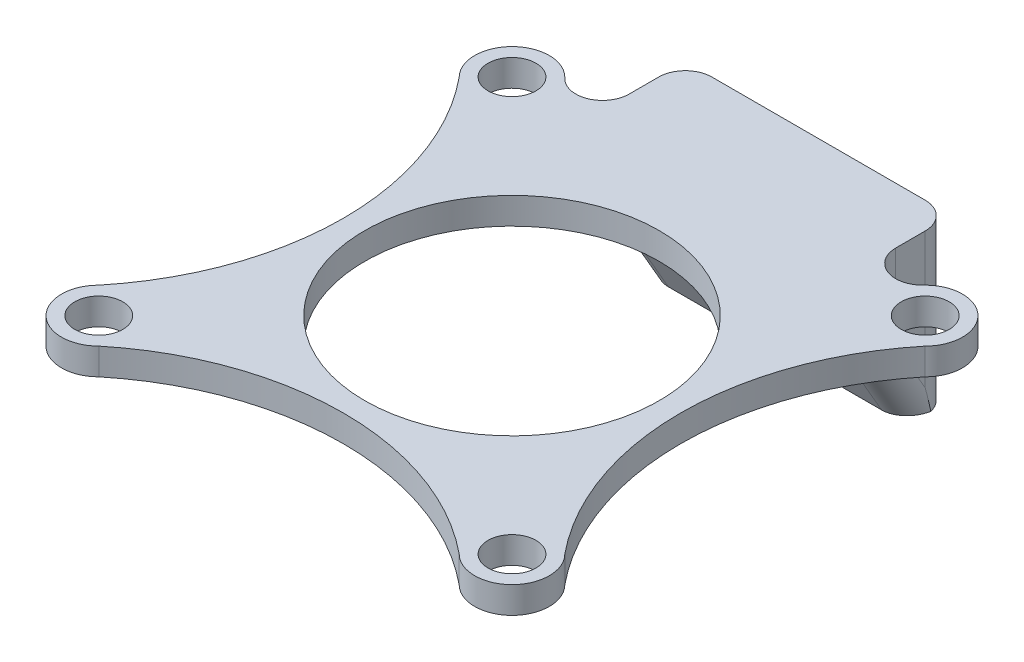
SolidWorks part; units mm, degrees
ref_plane "前视基准面" through (0, 0, 0) normal (0, 0, 1) x (1, 0, 0)
ref_plane "上视基准面" through (0, 0, 0) normal (0, 1, 0) x (1, 0, 0)
ref_plane "右视基准面" through (0, 0, 0) normal (1, 0, 0) x (0, 0, -1)
sketch "草图1" plane through (0, 0, 0) normal (0, 1, 0) x (1, 0, 0)
  line L0 (0, 80.3703) -> (0, -68.6055) construction
  line L1 (-122.6133, 0) -> (117.4549, 0) construction
  line L2 (-122.6133, -15.5) -> (117.4549, -15.5) construction
  line L3 (-15.5, 80.3703) -> (-15.5, -68.6055) construction
  line L4 (-122.6133, 15.5) -> (117.4549, 15.5) construction
  line L5 (15.5, 80.3703) -> (15.5, -68.6055) construction
  line L6 (15.5, 15.5) -> (-15.5, -15.5) construction
  line L7 (13.5201, 17.4799) -> (-17.4799, -13.5201)
  line L8 (17.4799, 13.5201) -> (-13.5201, -17.4799)
  line L9 (15.5, -15.5) -> (-15.5, 15.5) construction
  line L10 (17.4799, -13.5201) -> (-13.5201, 17.4799)
  line L11 (13.5201, -17.4799) -> (-17.4799, 13.5201)
  line L12 (-8, 23) -> (8, 23)
  line L13 (-122.6133, 16) -> (117.4549, 16) construction
  line L14 (-10, 21) -> (-10, 13.9598)
  line L15 (10, 21) -> (10, 13.9598)
  line L16 (-122.6133, 23) -> (117.4549, 23) construction
  line L17 (10, 80.3703) -> (10, -68.6055) construction
  line L19 (-10, 80.3703) -> (-10, -68.6055) construction
  circle A0 centre (0, 0) radius 11.05
  circle A3 centre (-15.5, 15.5) radius 1.8
  circle A4 centre (15.5, 15.5) radius 1.8
  circle A5 centre (15.5, -15.5) radius 1.8
  circle A6 centre (-15.5, -15.5) radius 1.8
  arc A24 (13.5201, 17.4799) -> (17.4799, 13.5201) centre (15.5, 15.5) cw
  arc A25 (-17.4799, -13.5201) -> (-13.5201, -17.4799) centre (-15.5, -15.5) ccw
  arc A26 (17.4799, -13.5201) -> (13.5201, -17.4799) centre (15.5, -15.5) cw
  arc A27 (-13.5201, 17.4799) -> (-17.4799, 13.5201) centre (-15.5, 15.5) ccw
  circle A28 centre (0, 0) radius 12.65
  arc A32 (-10, 21) -> (-8, 23) centre (-8, 21) cw
  arc A33 (8, 23) -> (10, 21) centre (8, 21) cw
  arc A34 (17.4799, 13.5201) -> (17.4799, -13.5201) centre (33.988, 0) ccw
  arc A35 (13.5201, -17.4799) -> (-13.5201, -17.4799) centre (0, -33.988) ccw
  arc A36 (-17.4799, 13.5201) -> (-17.4799, -13.5201) centre (-33.988, 0) cw
  point P26 (0, 0)
  dimension "D1" = 22.1
  dimension "D2" = 15.5
  dimension "D4" = 3.6
  dimension "D5" = 4
  dimension "D12" = 10
  dimension "D15" = 2
  dimension "D11" = 23
  dimension "D6" = 2.8
  dimension "D8" = 2.8
  dimension "D3" = 15.5
  dimension "D7" = 2.8
  dimension "D9" = 2.8
  dimension "D10" = 1.6
  dimension "D13" = 10
  dimension "D14" = 16
extrude "凸台-拉伸1" add sketch "草图1" along normal blind 2 contours A28 L8 A24 L7 A4 | L8 A28 L7 A0 | L7 A28 L10 A0 | L10 A28 L8 A0 | L11 A28 L10 A0 | L8 A28 L11 A0 | A28 L11 A26 L10 A5 | A28 L7 A25 L8 A6 | L11 A28 | A28 L8 | A28 L10 | L8 A28 | L11 A28 | A28 L7 | A28 L10 A27 L11 A3 | L10 A28 L11 A0 | L11 A28 L7 A0 | L7 A28 L8 A0 | A33 L12 A32 L14 L10 A28 L7 L15 region at (12.5044, 0, -12.5044) region at (0, 0, -17.4972) region at (13.1009, 0, -7.1299) region at (8.2996, 0, -8.2996) region at (0, 0, -11.2916) region at (11.2916, 0, 0) region at (13.1009, 0, 7.1299) region at (-12.5044, 0, -12.5044) region at (-8.2996, 0, -8.2996) region at (8.2996, 0, 8.2996) region at (12.5044, 0, 12.5044) region at (-13.1009, 0, -7.1299) region at (-11.2916, 0, 0) region at (0, 0, 11.2916) region at (7.1299, 0, 13.1009) region at (-13.1009, 0, 7.1299) region at (-7.1299, 0, 13.1009) region at (-8.2996, 0, 8.2996) region at (-12.5044, 0, 12.5044)
sketch "草图2" plane through (0, 0, 0) normal (0, -1, 0) x (1, 0, 0)
  line L0 (10, -13.9598) -> (-10, -13.9598)
  line L12 (10, -13.9598) -> (13.5201, -17.4799)
  line L14 (-13.5201, -17.4799) -> (-10, -13.9598)
  line L15 (-10, -13.9598) -> (-10, -21)
  line L16 (-8, -23) -> (8, -23)
  line L17 (10, -21) -> (10, -13.9598)
  line L23 (10, -13.9598) -> (13.5201, -17.4799)
  line L25 (-13.5201, -17.4799) -> (-10, -13.9598)
  line L26 (-10, -13.9598) -> (-10, -21)
  line L27 (-8, -23) -> (8, -23)
  line L28 (10, -21) -> (10, -13.9598)
  arc A9 (-13.5201, 17.4799) -> (13.5201, 17.4799) centre (0, 33.988) ccw
  arc A10 (-13.5201, 17.4799) -> (-17.4799, 13.5201) centre (-15.5, 15.5) ccw
  arc A11 (-13.5201, 17.4799) -> (13.5201, 17.4799) centre (0, 33.988) ccw
  arc A12 (-17.4799, -13.5201) -> (-13.5201, -17.4799) centre (-15.5, -15.5) ccw
  arc A13 (-10, -21) -> (-8, -23) centre (-8, -21) ccw
  arc A14 (8, -23) -> (10, -21) centre (8, -21) ccw
  arc A15 (13.5201, -17.4799) -> (17.4799, -13.5201) centre (15.5, -15.5) ccw
  arc A16 (-17.4799, -13.5201) -> (-17.4799, 13.5201) centre (-33.988, 0) ccw
  arc A17 (17.4799, 13.5201) -> (13.5201, 17.4799) centre (15.5, 15.5) ccw
  arc A19 (-13.5201, 17.4799) -> (-17.4799, 13.5201) centre (-15.5, 15.5) ccw
  arc A21 (-17.4799, -13.5201) -> (-13.5201, -17.4799) centre (-15.5, -15.5) ccw
  arc A22 (-10, -21) -> (-8, -23) centre (-8, -21) ccw
  arc A23 (8, -23) -> (10, -21) centre (8, -21) ccw
  arc A24 (13.5201, -17.4799) -> (17.4799, -13.5201) centre (15.5, -15.5) ccw
  arc A26 (17.4799, 13.5201) -> (13.5201, 17.4799) centre (15.5, 15.5) ccw
  arc A27 (-17.4799, -13.5201) -> (-17.4799, 13.5201) centre (-33.988, 0) ccw
  arc A28 (17.4799, 13.5201) -> (17.4799, -13.5201) centre (33.988, 0) ccw
  arc A29 (17.4799, 13.5201) -> (17.4799, -13.5201) centre (33.988, 0) ccw
  line M31 (-10, -13.9598) -> (-10, -21)
  arc M32 (-10, -21) -> (-8, -23) centre (-8, -21) ccw
  line M33 (-8, -23) -> (8, -23)
  arc M34 (8, -23) -> (10, -21) centre (8, -21) ccw
  line M35 (10, -21) -> (10, -13.9598)
  dimension "D1" = 0
extrude "凸台-拉伸2" add sketch "草图2" along normal blind 10 contours L0 M35 M31 M32 M33 M34 region at (0, 0, -18.4408)
sketch "草图3" plane through (0, 0, -23) normal (0, 0, -1) x (-1, 0, 0)
  line L0 (0, -12.2894) -> (0, 3.1293) construction
  line L1 (4.75, -12.2894) -> (4.75, 3.1293) construction
  line L2 (-4.75, -12.2894) -> (-4.75, 3.1293) construction
  line L3 (11.5377, -5) -> (-13.6892, -5) construction
  line L4 (8, -10) -> (-8, -10) construction
  circle A0 centre (4.75, -5) radius 0.75
  circle A1 centre (-4.75, -5) radius 0.75
  dimension "D4" = 1.5
  dimension "D5" = 1.5
  dimension "D1" = 4.75
  dimension "D3" = 5
  dimension "D2" = 4.75
extrude "切除-拉伸1" cut sketch "草图3" against normal blind 10
fillet "圆角3" radius 2 2 edges at (10, 1, -13.9598) (-10, 1, -13.9598)
chamfer "倒角1" distance 10 angle 30 1 edges at (0, -10, -13.9598) first distance on face at (-5.5, -5, -13.9598)
fillet "圆角1" radius 2 1 edges at (0, 0, -13.9598)
fillet "圆角2" radius 2 4 edges at (-10, -0.2679, -13.8051) (10, -0.2679, -13.8051) (-10, -5.5, -17.1352) (10, -5.5, -17.1352)
